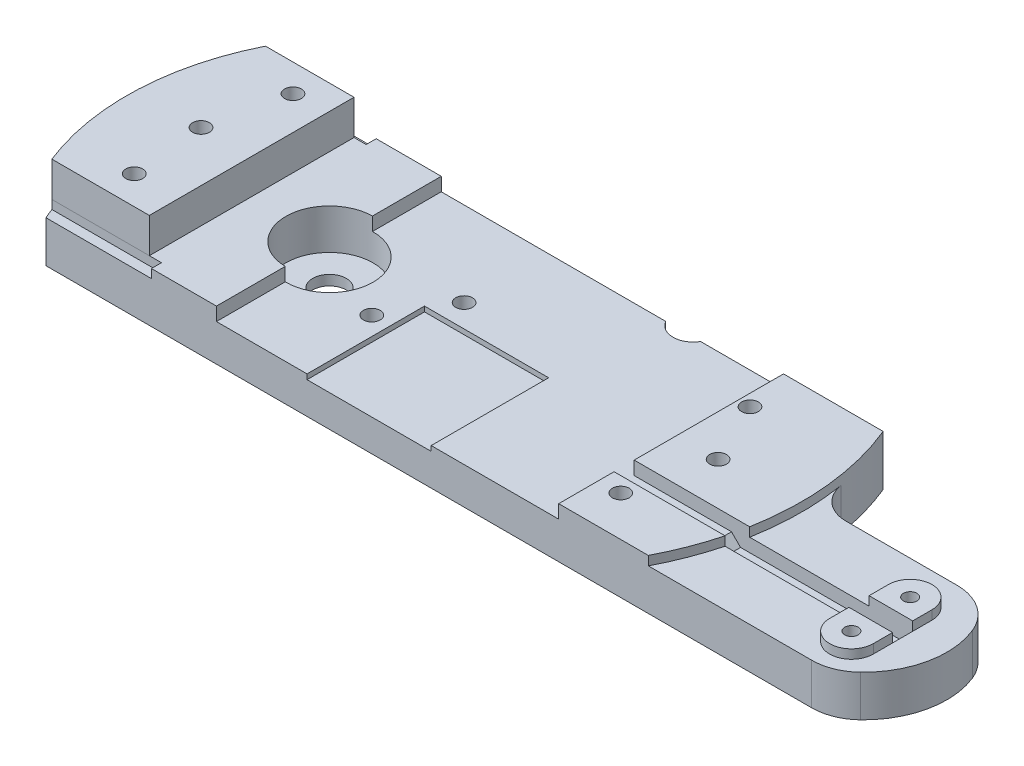
SolidWorks part; units mm, degrees
ref_plane "Front Plane" through (0, 0, 0) normal (0, 0, 1) x (1, 0, 0)
ref_plane "Top Plane" through (0, 0, 0) normal (0, 1, 0) x (1, 0, 0)
ref_plane "Right Plane" through (0, 0, 0) normal (1, 0, 0) x (0, 0, -1)
sketch "Sketch1" plane through (0, 0, 0) normal (0, 1, 0) x (1, 0, 0)
  line L1 (-97.5, -33.5) -> (97.5, -33.5)
  line L2 (-97.5, -33.5) -> (-97.5, 33.5)
  line L3 (-97.5, 33.5) -> (97.5, 33.5)
  line L4 (97.5, -33.5) -> (97.5, 33.5)
  line L5 (-97.5, -33.5) -> (97.5, 33.5) construction
  line L6 (-97.5, 33.5) -> (97.5, -33.5) construction
  point P0 (0, 0)
  dimension "D1" = 67
  dimension "D2" = 195
extrude "Boss-Extrude1" add sketch "Sketch1" along normal blind 25.4
sketch "Sketch2" plane through (0, 0, 0) normal (0, -1, 0) x (1, 0, 0)
  line L0 (-97.5, -33.5) -> (-97.5, 33.5) construction
  line L1 (97.5, 33.5) -> (97.5, -33.5) construction
  line L2 (97.5, 33.5) -> (88.5, 33.5)
  line L3 (-97.5, 33.5) -> (97.5, 33.5) construction
  line L4 (97.5, -33.5) -> (91.5, -33.5)
  line L5 (97.5, -33.5) -> (-97.5, -33.5) construction
  line L6 (-97.5, 33.5) -> (-91, 33.5)
  line L7 (-97.5, -33.5) -> (-88, -33.5)
  circle A0 centre (18.0922, -3.2198) radius 79.4078
  circle A1 centre (-22.6589, 2.9929) radius 74.8411
  line M7 (97.5, -33.5) -> (97.5, 33.5)
  line M8 (97.5, 33.5) -> (-97.5, 33.5)
  line M9 (-97.5, 33.5) -> (-97.5, -33.5)
  line M10 (-97.5, -33.5) -> (97.5, -33.5)
  dimension "D1" = 9
  dimension "D2" = 6
  dimension "D3" = 6.5
  dimension "D4" = 9.5
extrude "Cut-Extrude1" cut sketch "Sketch2" against normal through all contours A0 M7 M8 | A0 M10 M7 | A1 M9 M10 | A1 M8 M9 region at (94.8284, 0, 24.4273) region at (95.7123, 0, -25.9883) region at (-95.5654, 0, 25.941) region at (-94.6839, 0, -24.4966)
sketch "Sketch3" plane through (0, 0, 33.5) normal (0, 0, -1) x (-1, 0, 0)
  line L0 (97.5, 25.4) -> (63.2, 25.4)
  line L2 (63.2, 25.4) -> (63.2, 15)
  line L3 (63.2, 15) -> (40.2, 15)
  line L4 (40.2, 15) -> (40.2, 11)
  line L5 (40.2, 11) -> (-61.8, 11)
  line L6 (-91.5, 25.4) -> (88, 25.4) construction
  line L10 (97.5, 0) -> (97.5, 25.4) construction
  line L11 (-61.8, 11) -> (-61.8, 15)
  line L12 (-61.8, 15) -> (-97.5, 15)
  line L13 (-97.5, 25.4) -> (-97.5, 0) construction
  line L14 (-97.5, 15) -> (-97.5, 25.4)
  line L15 (-97.5, 25.4) -> (63.2, 25.4)
  line M13 (-88.5, 0) -> (-88.5, 25.4)
  line M14 (-88.5, 25.4) -> (91, 25.4)
  dimension "D1" = 10.4
  dimension "D2" = 34.3
  dimension "D3" = 23
  dimension "D4" = 4
  dimension "D5" = 102
extrude "Cut-Extrude2" cut sketch "Sketch3" along normal through all contours L11 L12 L2 L3 L4 L5 M13 M14 | L2 L3 L4 L5 L11 L12 L14 L15 region at (12.2699, 18.7206, 33.5)
sketch "Sketch4" plane through (0, 25.4, 0) normal (0, 1, 0) x (1, 0, 0)
  line L0 (-59.5873, 33.5) -> (-59.5873, 30.5)
  line L1 (-63.2, 33.5) -> (-88, 33.5) construction
  line L2 (-59.5873, 30.5) -> (-89.5873, 30.5)
  line L3 (-59.5873, -33.5) -> (-59.5873, -30.5)
  line L4 (-91, -33.5) -> (-63.2, -33.5) construction
  line L5 (-59.5873, -30.5) -> (-92.2617, -30.5)
  line L6 (-59.5873, 33.5) -> (-63.2, 33.5)
  line L7 (-59.5873, -33.5) -> (-63.2, -33.5)
  arc A0 (-88, 33.5) -> (-91, -33.5) centre (-22.6589, -2.9929) ccw construction
  line M5 (-91, -33.5) -> (-63.2, -33.5)
  line M6 (-63.2, -33.5) -> (-63.2, 33.5)
  line M7 (-63.2, 33.5) -> (-88, 33.5)
  arc M8 (-88, 33.5) -> (-91, -33.5) centre (-22.6589, -2.9929) ccw
  dimension "D1" = 3
  dimension "D2" = 3
  dimension "D3" = 30
extrude "Cut-Extrude3" cut sketch "Sketch4" against normal blind 13 contours L2 M6 M7 M8 | L0 L6 L2 M6 | L5 M6 M8 M5 | L7 L3 L5 M6 region at (-61.3937, 25.4, -32) region at (-76.0082, 25.4, -31.9845) region at (-77.4242, 25.4, 31.9889) region at (-61.3937, 25.4, 32)
sketch "Sketch6" plane through (0, 0, 0) normal (0, -1, 0) x (1, 0, 0)
  line L0 (-63.2, -33.5) -> (-97.5, -33.5)
  line L1 (91.5, -33.5) -> (-88, -33.5) construction
  line L2 (-63.2, -33.5) -> (-63.2, 33.5)
  line L3 (-91, 33.5) -> (88.5, 33.5) construction
  line L4 (-63.2, -9) -> (-28.1, -9) construction
  line L5 (-63.2, 8.7) -> (-18.7, 8.7) construction
  line L6 (-63.2, -8.3) -> (-8.2, -8.3) construction
  line L8 (91.5, -33.5) -> (-88, -33.5) construction
  line L9 (-97.5, -33.5) -> (-97.5, 33.5)
  line L10 (-97.5, 33.5) -> (-63.2, 33.5)
  circle A1 centre (-18.7, 8.7) radius 2.5
  circle A2 centre (74.1, -1.7) radius 2.5
  circle A3 centre (68.3, 21.5) radius 2.5
  circle A4 centre (65.3, -20) radius 2.5
  circle A5 centre (-8.2, -8.3) radius 2.5
  circle A6 centre (-76.2, 22) radius 2.5
  circle A7 centre (-78.2, 0.1) radius 2.5
  circle A8 centre (-73.2, -22.3) radius 2.5
  arc A10 (-91, 33.5) -> (-88, -33.5) centre (-22.6589, 2.9929) ccw construction
  dimension "D22" = 5
  dimension "D3" = 35.1
  dimension "D4" = 34.3
  dimension "D5" = 44.5
  dimension "D6" = 24.5
  dimension "D7" = 55
  dimension "D8" = 42.2
  dimension "D9" = 137.3
  dimension "D10" = 128.5
  dimension "D11" = 131.5
  dimension "D12" = 10
  dimension "D13" = 15
  dimension "D14" = 13
  dimension "D15" = 11.2
  dimension "D16" = 33.6
  dimension "D17" = 55.5
  dimension "D18" = 31.8
  dimension "D19" = 55
  dimension "D20" = 13.5
  dimension "D21" = 25.2
extrude "Cut-Extrude4" cut sketch "Sketch6" against normal through all contours A5 | A1 | A6 | A7 | A8 | A4 | A2 | A3 region at (-18.7, 0, 8.7) region at (74.1, 0, -1.7) region at (68.3, 0, 21.5) region at (65.3, 0, -20) region at (-8.2, 0, -8.3) region at (-76.2, 0, 22) region at (-78.2, 0, 0.1) region at (-73.2, 0, -22.3)
sketch "Sketch7" plane through (0, 11, 0) normal (0, 1, 0) x (1, 0, 0)
  line L1 (-13.2, 1.5) -> (23.8, 1.5)
  line L2 (-13.2, 1.5) -> (-13.2, -33.5)
  line L3 (-13.2, -33.5) -> (23.8, -33.5)
  line L4 (23.8, 1.5) -> (23.8, -33.5)
  line L8 (-63.2, 30.5) -> (-63.2, -30.5) construction
  line L9 (-63.2, 30.5) -> (-63.2, -30.5) construction
  line L10 (-40.2, -33.5) -> (61.8, -33.5) construction
  dimension "D1" = 50
  dimension "D2" = 87
  dimension "D3" = 35
extrude "Cut-Extrude5" cut sketch "Sketch7" against normal blind 1.5
sketch "Sketch8" plane through (0, 25.4, 0) normal (0, 1, 0) x (1, 0, 0)
  line L0 (-59.5873, -33.5) -> (-97.5, -33.5)
  line L1 (-97.5, -33.5) -> (-97.5, 33.5)
  line L3 (-97.5, 33.5) -> (31.9, 33.5)
  line L6 (31.9, 36.5) -> (31.9, 30.5)
  line L7 (31.9, 33.5) -> (37.0962, 33.5)
  line L10 (-59.5873, 33.5) -> (-88, 33.5) construction
  line L11 (-40.2, 33.5) -> (61.8, 33.5) construction
  circle A1 centre (31.9, 36.5) radius 6
  arc A2 (-89.5873, 30.5) -> (-92.2617, -30.5) centre (-22.6589, -2.9929) ccw construction
  dimension "D1" = 12
  dimension "D2" = 129.4
extrude "Cut-Extrude6" cut sketch "Sketch8" against normal blind 18.5 contours L6 A1 L7 | L3 A1 L6 region at (29.8648, 25.4, -32.2699) region at (33.9352, 25.4, -32.2699)
sketch "Sketch9" plane through (0, 0, 0) normal (0, -1, 0) x (1, 0, 0)
  line L0 (88.5, 33.5) -> (137.2004, 33.5)
  line L1 (139.5727, -7.5) -> (97.3846, -7.5)
  arc A0 (153.4738, 1.8643) -> (147.5429, 29.3643) centre (130.3054, 11.2571) ccw
  arc A1 (91.5, -33.5) -> (88.5, 33.5) centre (18.0922, -3.2198) ccw construction
  arc A2 (142.3827, -10.6321) -> (147.5429, 29.3643) centre (130.3054, 11.2571) ccw construction
  arc A3 (147.5429, 29.3643) -> (137.2004, 33.5) centre (137.2004, 18.5) ccw
  arc A4 (147.5429, 29.3643) -> (137.9704, 33.4802) centre (137.2004, 18.5) ccw construction
  arc A5 (139.5727, -7.5) -> (153.4738, 1.8643) centre (139.5727, 7.5) ccw
  circle A6 centre (112.8181, -27.5) radius 16 construction
  circle A7 centre (103.4238, 59.4942) radius 16 construction
  circle A8 centre (112.8181, -27.5) radius 20 construction
  arc A9 (97.3846, -7.5) -> (88.5, 33.5) centre (18.0922, -3.2198) ccw
  circle A10 centre (138.3, 5.25) radius 2
  circle A11 centre (138.3, 22.75) radius 2
  circle A12 centre (138.3, 22.75) radius 2 construction
  circle A13 centre (138.3, 5.25) radius 2 construction
  dimension "D1" = 4
extrude "Boss-Extrude2" add sketch "Sketch9" against normal offset from surface (12.3 mm away) 1.3 up to face at (-16.2, 11, 8.7) offset beyond the face yes
fillet "Fillet1" radius 10 1 edges at (97.3846, 6.15, -7.5)
sketch "Sketch10" plane through (0, 0, 0) normal (0, -1, 0) x (1, 0, 0)
  circle A0 centre (-40.0178, 0) radius 13
  dimension "D1" = 26
extrude "Cut-Extrude7" cut sketch "Sketch10" against normal up to surface (15 mm away) from offset 3 up to face at (-55.6437, 15, 0) offset against normal yes
sketch "Sketch13" plane through (0, 0, 0) normal (0, -1, 0) x (1, 0, 0)
  circle A0 centre (-40.0178, 0) radius 5
  dimension "D1" = 10
extrude "Cut-Extrude9" cut sketch "Sketch13" against normal through all
sketch "Sketch11" plane through (0, 12.3, 0) normal (0, 1, 0) x (1, 0, 0)
  line L0 (138.3, -5.25) -> (138.3, -22.75) construction
  line L1 (144.8, -5.25) -> (144.8, -22.75)
  line L2 (131.8, -5.25) -> (131.8, -22.75)
  line L3 (131.8, -11) -> (144.8, -11)
  line L4 (131.8, -17) -> (144.8, -17)
  line L5 (131.8, -14) -> (144.8, -14) construction
  arc A0 (144.8, -5.25) -> (131.8, -5.25) centre (138.3, -5.25) ccw
  arc A1 (131.8, -22.75) -> (144.8, -22.75) centre (138.3, -22.75) ccw
  point P4 (138.3, -14)
  circle M15 centre (138.3, -22.75) radius 2
  circle M16 centre (138.3, -5.25) radius 2
  dimension "D1" = 13
  dimension "D2" = 6
extrude "Boss-Extrude3" add sketch "Sketch11" along normal up to surface (2.7 mm away) contours L1 A0 L2 L3 M16 | L2 A1 L1 L4 M15 region at (144.6214, 12.3, 8.125) region at (144.6214, 12.3, 19.875) up to face at (70.8, 15, 21.5)
split "Split1" bodies to split 113 resulting bodies 114 115 split by face at (-53.8367, 15, 0)
sketch "Sketch12" plane through (0, 0, 11) normal (0, 0, 1) x (1, 0, 0)
  line L0 (144.8, 15) -> (144.8, 8.3)
  line L1 (144.8, 8.3) -> (93.5, 8.3)
  line L3 (97.5, 12.3) -> (88.5, 12.3) construction
  line L4 (90.8, 11) -> (61.8, 11)
  line L5 (61.8, 11) -> (61.8, 15)
  line L6 (61.8, 15) -> (88.5, 15) construction
  line L7 (61.8, 15) -> (144.8, 15)
  line L10 (97.5, 12.3) -> (93.5, 12.3) construction
  line L12 (88.5, 12.3) -> (137.2004, 12.3) construction
  line L13 (93.5, 12.3) -> (93.5, 8.3) construction
  line L14 (61.8, 11) -> (61.8, 15) construction
  line L15 (23.8, 11) -> (61.8, 11) construction
  line L16 (93.5, 8.3) -> (90.8, 11)
  dimension "D1" = 45
extrude "Cut-Extrude8" cut sketch "Sketch12" along normal up to surface (6 mm away) up to face at (138.3, 13.65, 17)
